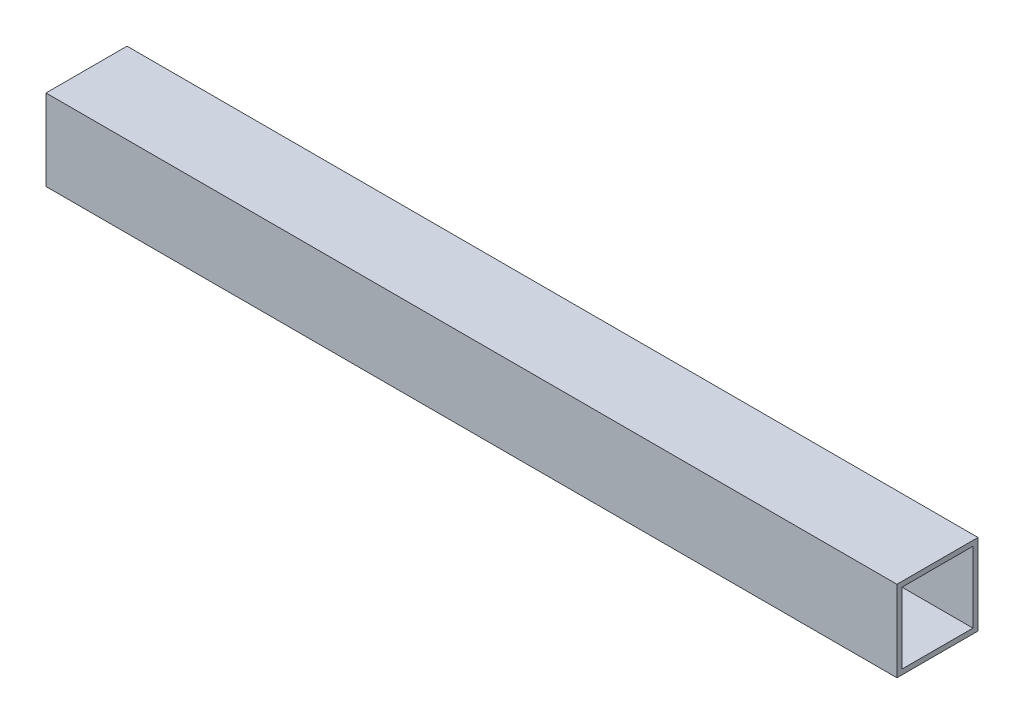
SolidWorks part; units mm, degrees
material "6061-T6 (SS)"
ref_plane "Front" through (0, 0, 0) normal (0, 0, 1) x (1, 0, 0)
ref_plane "Top" through (0, 0, 0) normal (0, 1, 0) x (1, 0, 0)
ref_plane "Right" through (0, 0, 0) normal (1, 0, 0) x (0, 0, -1)
sketch "Sketch1" plane through (0, 0, 0) normal (1, 0, 0) x (0, 0, -1)
  line L1 (12.7, -12.7) -> (-12.7, -12.7)
  line L2 (12.7, -12.7) -> (12.7, 12.7)
  line L3 (12.7, 12.7) -> (-12.7, 12.7)
  line L4 (-12.7, -12.7) -> (-12.7, 12.7)
  line L5 (12.7, -12.7) -> (-12.7, 12.7) construction
  line L6 (12.7, 12.7) -> (-12.7, -12.7) construction
  point P0 (0, 0)
  dimension "D1" = 25.4
extrude "Extrude-Thin1" add sketch "Sketch1" along normal up to surface (266.7 mm away) thin thin type one direction reverse wall 1.5875
